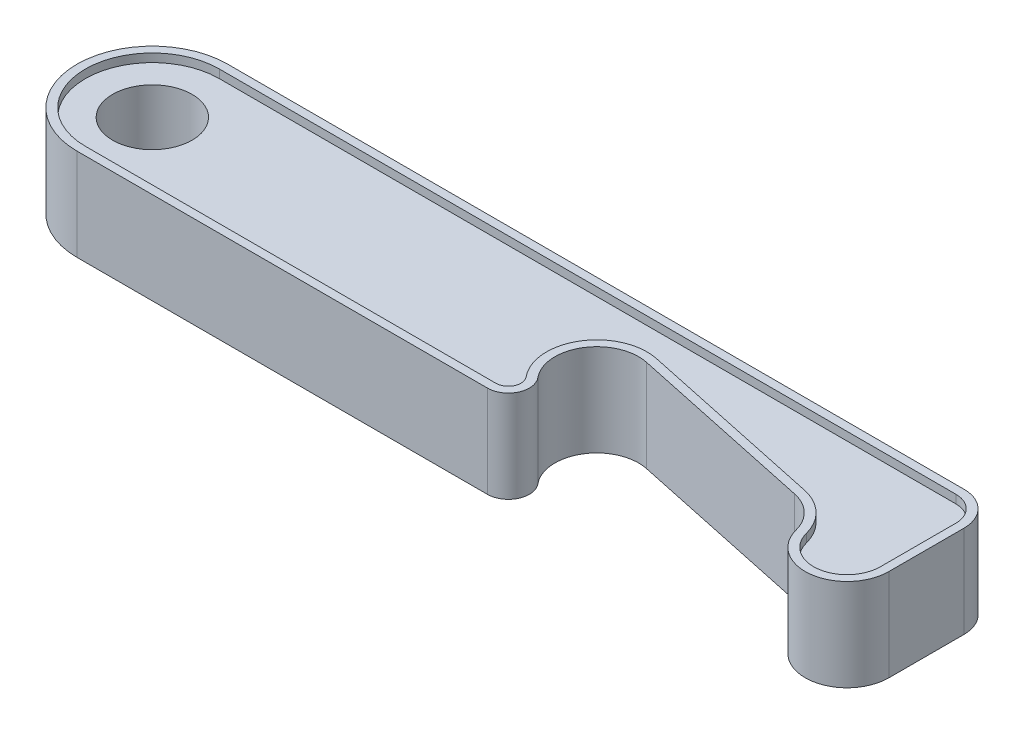
SolidWorks part; units mm, degrees
ref_plane "Front Plane" through (0, 0, 0) normal (0, 0, 1) x (1, 0, 0)
ref_plane "Top Plane" through (0, 0, 0) normal (0, 1, 0) x (1, 0, 0)
ref_plane "Right Plane" through (0, 0, 0) normal (1, 0, 0) x (0, 0, -1)
sketch "Sketch1" plane through (0, 0, 0) normal (0, 1, 0) x (1, 0, 0)
  line L0 (-19.3737, 0) -> (123.9252, 0) construction
  line L1 (88, 9) -> (0, 9)
  line L2 (49.0402, -9) -> (0, -9)
  line L3 (92, 5) -> (92, -4)
  line L4 (78.3571, -1.6093) -> (55.8571, 3.1733)
  line L5 (88, 8) -> (0, 8)
  line L6 (49.0402, -8) -> (0, -8)
  line L7 (78.565, -0.6311) -> (56.065, 4.1514)
  line L8 (91, 5) -> (91, -4)
  circle A0 centre (0, 0) radius 4.75
  arc A1 (0, 9) -> (0, -9) centre (0, 0) ccw
  arc A2 (88, 9) -> (92, 5) centre (88, 5) cw
  arc A3 (92, -4) -> (82.1588, -5.25) centre (87, -4) cw
  arc A4 (82.1588, -5.25) -> (78.3571, -1.6093) centre (77.3175, -6.5) ccw
  arc A5 (55.8571, 3.1733) -> (50.966, -4.9058) centre (54.8175, -1.7175) ccw
  arc A6 (50.966, -4.9058) -> (49.0402, -9) centre (49.0402, -6.5) cw
  arc A7 (0, 8) -> (0, -8) centre (0, 0) ccw
  arc A8 (50.1957, -5.5435) -> (49.0402, -8) centre (49.0402, -6.5) cw
  arc A9 (56.065, 4.1514) -> (50.1957, -5.5435) centre (54.8175, -1.7175) ccw
  arc A10 (83.127, -5) -> (78.565, -0.6311) centre (77.3175, -6.5) ccw
  arc A11 (91, -4) -> (83.127, -5) centre (87, -4) cw
  arc A12 (88, 8) -> (91, 5) centre (88, 5) cw
  point P21 (92, -0.4275)
  point P22 (82.0742, -12.5274)
  point P23 (0, 0)
  point P24 (0, -9)
  point P25 (0, 9)
  dimension "D1" = 9.5
  dimension "D3" = 18
  dimension "D4" = 4
  dimension "D5" = 92
  dimension "D6" = 5
  dimension "D7" = 5
  dimension "D8" = 2.5
  dimension "D9" = 5
  dimension "D2" = 18
  dimension "D10" = 12
  dimension "D11" = 0
  dimension "D12" = 5
  dimension "D13" = 22.5
  dimension "D14" = 1
extrude "Boss-Extrude1" add sketch "Sketch1" along normal blind 4.5 and the other way blind 4.5 contours L0 A7 L6 A8 A9 A0 | A7 L0 A0 A9 L7 L8 A12 L5 | L0 L7 A10 A11 L8 region at (42.836, 0, -4.2802) region at (23.4452, 0, 4.1222) region at (86.1686, 0, 3.2778)
extrude "Boss-Extrude2" add sketch "Sketch1<3>" along normal blind 5.5 and the other way blind 5.5 contours A9 L0 A5 L4 L7 | L0 L4 A4 A3 L3 L8 A11 A10 L7 | A1 L0 A7 L5 A12 L8 L3 A2 L1 | L0 A1 L2 A6 A5 A9 A8 L6 A7 region at (-6.2923, 0, -6.2923) region at (-8.5, 0, 0.6121) region at (51.8929, 0, -3.2114) region at (91.7696, 0, 2)
sketch "Sketch1<3>" plane through (0, 0, 0) normal (0, 1, 0) x (1, 0, 0) same geometry as "Sketch1"
